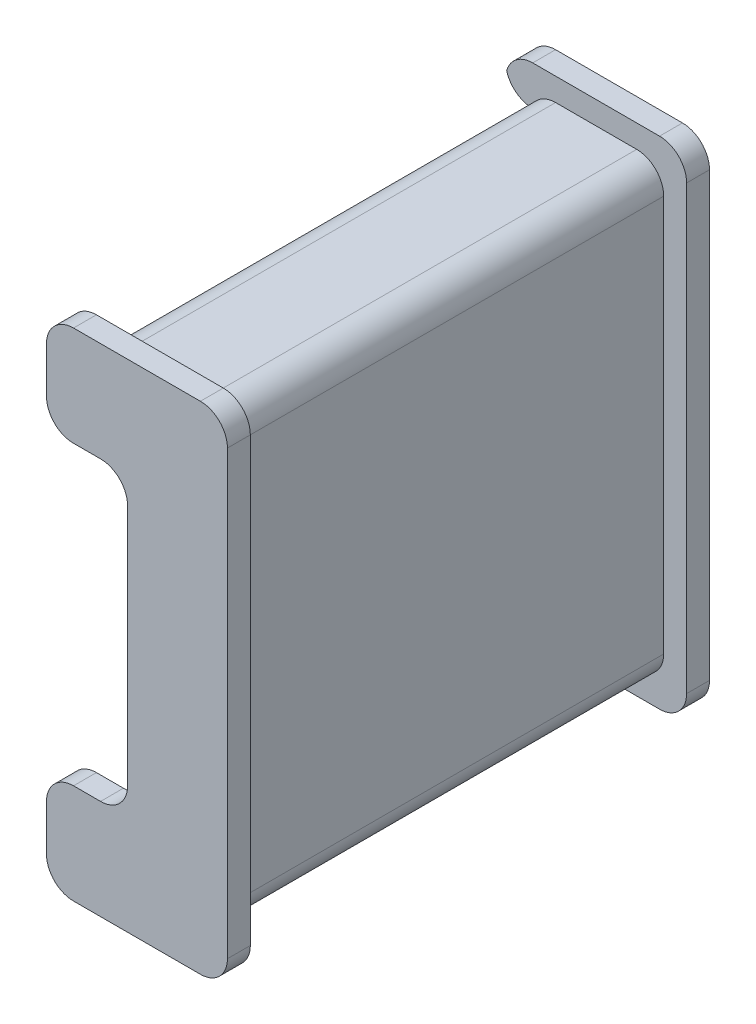
SolidWorks part; units mm, degrees
material "ABS"
ref_plane "X-Y Datum" through (0, 0, 0) normal (0, 0, 1) x (1, 0, 0)
ref_plane "X-Z Datum" through (0, 0, 0) normal (0, 1, 0) x (1, 0, 0)
ref_plane "Y-Z Datum" through (0, 0, 0) normal (1, 0, 0) x (0, 0, -1)
sketch "Sketch1" plane through (0, 0, 0) normal (0, 0, 1) x (1, 0, 0)
  line L1 (0, 0) -> (15, 0)
  line L2 (0, 0) -> (0, 6)
  line L3 (0, 6) -> (9, 6)
  line L4 (15, 0) -> (15, -1)
  line L6 (15, -1) -> (15, 50)
  line L8 (9, 6) -> (9, 44)
  line L9 (15, 50) -> (0, 50)
  line L10 (15, 50) -> (15, 46.6041)
  line L11 (9, 44) -> (0, 44)
  line L12 (0, 50) -> (0, 44)
  point P12 (0, 47)
  dimension "D1" = 15
  dimension "D2" = 50
  dimension "D3" = 6
  dimension "D4" = 6
  dimension "D5" = 6
  dimension "D6" = 15
extrude "Boss-Extrude1" add sketch "Sketch1" along normal blind 48.42 contours L9 L12 L11 L8 L3 L2 L1 L4 L6 region at (10.0147, 25, 0)
sketch "Sketch2" plane through (0, 0, 48.42) normal (0, 0, 1) x (1, 0, 0)
  line L17 (-2.54, 41.46) -> (6.46, 41.46)
  line L18 (-2.54, 52.54) -> (17.54, 52.54)
  line L19 (17.54, 52.54) -> (17.54, -2.54)
  line L20 (17.54, -2.54) -> (-2.54, -2.54)
  line L21 (-2.54, 8.54) -> (6.46, 8.54)
  line L22 (6.46, 41.46) -> (6.46, 8.54)
  line L23 (9, 6) -> (9, 44) construction
  line L24 (15, 0) -> (15, 50) construction
  line L25 (15, 50) -> (0, 50) construction
  line L26 (9, 44) -> (0, 44) construction
  line L27 (0, 6) -> (9, 6) construction
  line L28 (0, 0) -> (15, 0) construction
  line L29 (-2.54, 52.54) -> (-2.54, 41.46)
  line L30 (-2.54, 8.54) -> (-2.54, -2.54)
  dimension "D2" = 2.54
  dimension "D3" = 2.54
  dimension "D4" = 2.54
  dimension "D5" = 2.54
  dimension "D6" = 2.54
  dimension "D8" = 2.54
extrude "Boss-Extrude2" add sketch "Sketch2" along normal blind 2.54
sketch "Sketch3" plane through (0, 0, 0) normal (0, 0, -1) x (-1, 0, 0)
  line L24 (-17.54, -2.54) -> (-17.54, 52.54) construction
  line L29 (2.54, 52.54) -> (-17.54, 52.54)
  line L30 (2.54, 52.54) -> (2.54, 48.1569)
  line L31 (2.54, 48.1569) -> (-6.46, 48.1569)
  line L32 (-17.54, 52.54) -> (-17.54, 48.1569)
  line L33 (2.54, -2.54) -> (-17.54, -2.54) construction
  line L35 (-17.54, 48.1569) -> (-17.54, -2.54)
  line L36 (-17.54, -2.54) -> (-6.46, -2.54)
  line L37 (-6.46, 48.1569) -> (-6.46, 8.54)
  line L39 (-6.46, -2.54) -> (2.54, -2.54)
  line L41 (-6.46, 8.54) -> (2.54, 8.54)
  line L42 (2.54, -2.54) -> (2.54, 8.54)
extrude "Boss-Extrude3" add sketch "Sketch3" along normal blind 2.54
fillet "Fillet4" radius 3 8 edges at (0, 6, 24.21) (9, 6, 24.21) (15, 0, 24.21) (0, 0, 24.21) (15, 50, 24.21) (0, 50, 24.21) (9, 44, 24.21) (0, 44, 24.21)
fillet "Fillet5" radius 3 16 edges at (-2.54, 52.54, -1.27) (17.54, 52.54, -1.27) (17.54, -2.54, -1.27) (-2.54, -2.54, -1.27) (-2.54, 8.54, -1.27) (6.46, 8.54, -1.27) (-2.54, 48.1569, -1.27) (6.46, 48.1569, -1.27) (-2.54, 8.54, 49.69) (6.46, 8.54, 49.69) (17.54, -2.54, 49.69) (-2.54, -2.54, 49.69) (17.54, 52.54, 49.69) (-2.54, 52.54, 49.69) (6.46, 41.46, 49.69) (-2.54, 41.46, 49.69)
